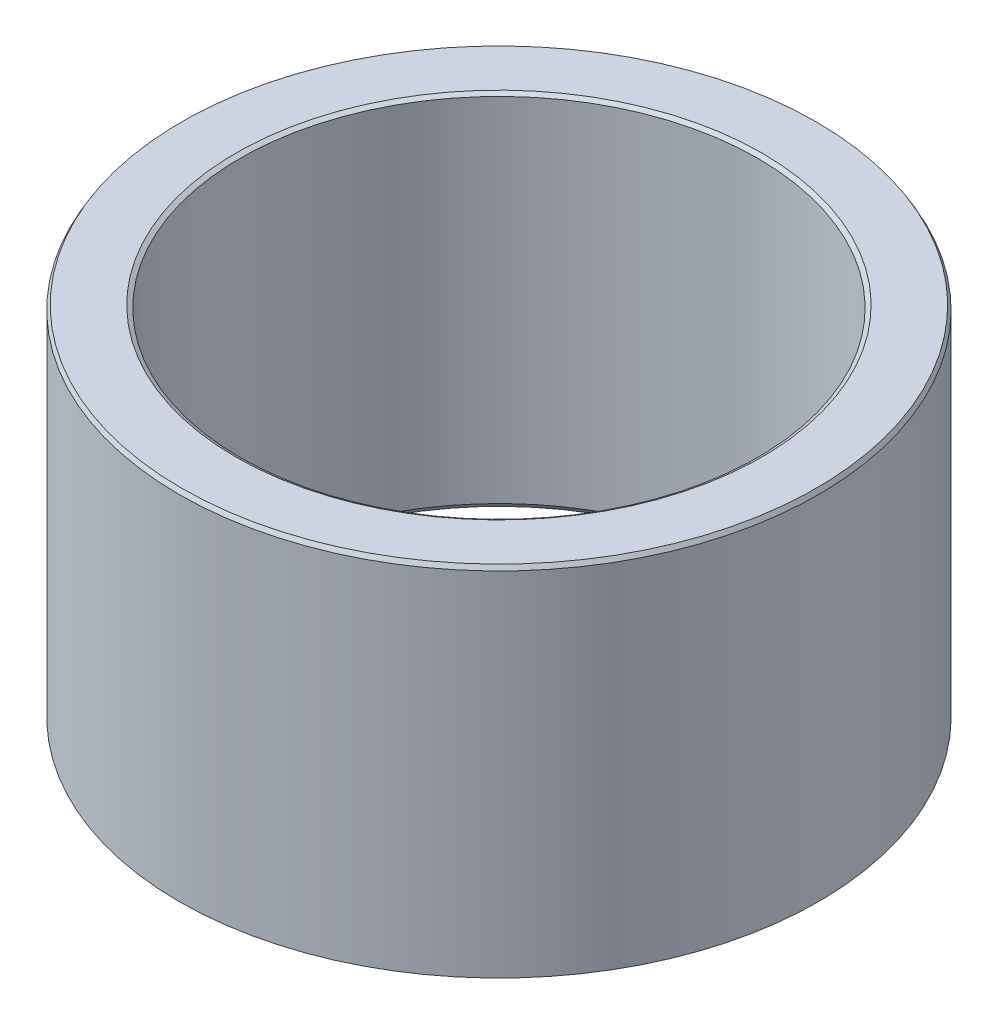
SolidWorks part; units mm, degrees
ref_plane "Front Plane" through (0, 0, 0) normal (0, 0, 1) x (1, 0, 0)
ref_plane "Top Plane" through (0, 0, 0) normal (0, 1, 0) x (1, 0, 0)
ref_plane "Right Plane" through (0, 0, 0) normal (1, 0, 0) x (0, 0, -1)
sketch "Sketch1" plane through (0, 0, 0) normal (0, 1, 0) x (1, 0, 0)
  circle A0 centre (0, 0) radius 30
  dimension "SLEEVE_OD" = 60
extrude "Boss-Extrude1" add sketch "Sketch1" along normal blind 33.7032
sketch "Sketch2" plane through (0, 0, 0) normal (0, 1, 0) x (1, 0, 0)
  circle A0 centre (0, 0) radius 24.2965
  dimension "BORE_D" = 48.5929
extrude "Cut-Extrude1" cut sketch "Sketch2" along normal through all
chamfer "Chamfer1" distance 0.397 angle 30 4 edges at (0, 33.7032, 24.2965) (0, 0, 24.2965) (0, 0, 30) (0, 33.7032, 30) first distance on face at (0, 33.7032, 24.2965) first distance on face at (0, 0, 24.2965) first distance on face at (0, 33.7032, 30)
